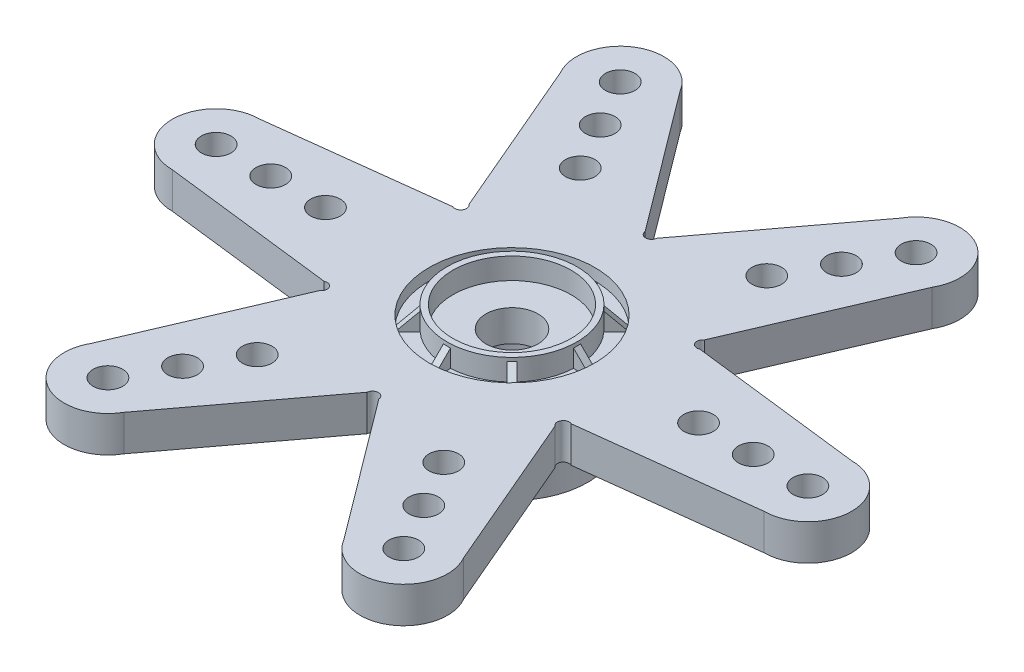
SolidWorks part; units mm, degrees
ref_plane "Front Plane" through (0, 0, 0) normal (0, 0, 1) x (1, 0, 0)
ref_plane "Top Plane" through (0, 0, 0) normal (0, 1, 0) x (1, 0, 0)
ref_plane "Right Plane" through (0, 0, 0) normal (1, 0, 0) x (0, 0, -1)
sketch "Sketch1" plane through (0, 0, 0) normal (0, 1, 0) x (1, 0, 0)
  line L0 (5.7752, -3.8298) -> (0, 0)
  line L1 (6.3503, 3.495) -> (6.3503, 3.8298)
  line L2 (6.3497, -3.4899) -> (15.8747, -2.3469)
  line L3 (6.3503, 3.495) -> (15.8747, 2.3521)
  line L4 (5.7752, 3.8298) -> (0, 0)
  line L5 (6.3503, 3.8298) -> (5.7752, 3.8298)
  line L6 (6.3497, -3.4899) -> (6.3497, -3.8298)
  line L7 (6.3497, -3.8298) -> (5.7752, -3.8298)
  arc A0 (15.8747, -2.3469) -> (15.8747, 2.3521) centre (15.8747, 0.0026) ccw
  dimension "D2" = 4.699
extrude "Extrude4" add sketch "Sketch1" along normal blind 1.9304
sketch "Sketch2" plane through (0, 1.9304, 0) normal (0, 1, 0) x (-1, 0, 0)
  circle A0 centre (-6.3426, -4.1499) radius 0.6604
  circle A1 centre (-6.3426, 4.1499) radius 0.6604
  dimension "D1" = 1.3208
extrude "Cut-Extrude1" cut sketch "Sketch2" against normal through all contours A1 | A0
ref_axis "Axis1" through (0, 0, 0) along (0, 1, 0)
pattern_circular "CirPattern4" count 6 over 360 about axis through (0, 0, 0) along (0, 1, 0) of "Extrude4"
sketch "Sketch3" plane through (0, 1.9304, 0) normal (0, 1, 0) x (-1, 0, 0)
  circle A0 centre (0, 0) radius 1.397
  dimension "D1" = 2.794
extrude "Cut-Extrude2" cut sketch "Sketch3" against normal blind 12.7 and the other way blind 12.7
sketch "Sketch4" plane through (0, 1.9304, 0) normal (0, 1, 0) x (-1, 0, 0)
  circle A0 centre (0, 0) radius 4.445
  dimension "D1" = 8.89
extrude "Cut-Extrude3" cut sketch "Sketch4" against normal blind 0.635
sketch "Sketch5" plane through (0, 1.2954, 0) normal (0, 1, 0) x (-1, 0, 0)
  circle A0 centre (0, 0) radius 3.4925
  circle A1 centre (0, 0) radius 3.175
  dimension "D1" = 6.985
  dimension "D2" = 6.35
extrude "Extrude5" add sketch "Sketch5" along normal blind 1.143 contours A1 | A0
sketch "Sketch8" plane through (0, 0, 0) normal (0, 0, 1) x (1, 0, 0)
  line L1 (4.445, 1.2954) -> (-4.445, 1.2954) construction
  line L4 (-3.4925, 2.2448) -> (-4.443, 1.2954)
rib "Rib10" sketch "Sketch8" sketch "Sketch8" thickness 0.381 extrusion direction parallel to sketch draft on no parameters "D1"=0.381
pattern_circular "CirPattern5" count 8 over 360 about axis through (0, 0, 0) along (0, 1, 0) of "Rib10"
sketch "Sketch9" plane through (0, 1.9304, 0) normal (0, 1, 0) x (-1, 0, 0)
  circle A0 centre (7.9351, 13.7492) radius 0.7937
  circle A2 centre (6.4692, 11.2092) radius 0.7937
  circle A3 centre (5.0033, 8.6692) radius 0.7937
  dimension "D2" = 2.54
  dimension "D3" = 2.54
extrude "Cut-Extrude4" cut sketch "Sketch9" against normal through all
pattern_circular "CirPattern6" count 6 over 360 about axis through (0, 0, 0) along (0, 1, 0) of "Cut-Extrude4"
sketch "Sketch10" plane through (0, 0, 0) normal (0, -1, 0) x (1, 0, 0)
  circle A0 centre (0, 0) radius 5.08
  dimension "D1" = 10.16
extrude "Extrude6" add sketch "Sketch10" along normal blind 0.762
fillet "Fillet2" radius 0.508 1 edges at (0, 0, 5.08)
sketch "Sketch11" plane through (0, -0.762, 0) normal (0, -1, 0) x (1, 0, 0)
  circle A0 centre (0, 0) radius 4.064
  dimension "D1" = 8.128
extrude "Extrude7" add sketch "Sketch11" along normal blind 3.048
fillet "Fillet3" radius 0.889 1 edges at (0, -0.762, -4.064)
sketch "Sketch12" plane through (0, -3.81, 0) normal (0, -1, 0) x (1, 0, 0)
  circle A0 centre (0, 0) radius 2.8575
  dimension "D1" = 5.715
extrude "Cut-Extrude5" cut sketch "Sketch12" against normal blind 3.429
sketch "Sketch14" plane through (0, -0.381, 0) normal (0, -1, 0) x (1, 0, 0)
  circle A0 centre (0, 0) radius 1.397
  dimension "D1" = 2.794
extrude "Cut-Extrude6" cut sketch "Sketch14" against normal through all
sketch "Sketch15" plane through (0, 1.9304, 0) normal (0, 1, 0) x (-1, 0, 0)
  circle A0 centre (-6.4872, -3.7519) radius 0.3175
  dimension "D1" = 0.635
extrude "Cut-Extrude7" cut sketch "Sketch15" against normal through all and the other way through all
pattern_circular "CirPattern7" count 6 over 360 about axis through (0, 0, 0) along (0, 1, 0) of "Cut-Extrude7"
